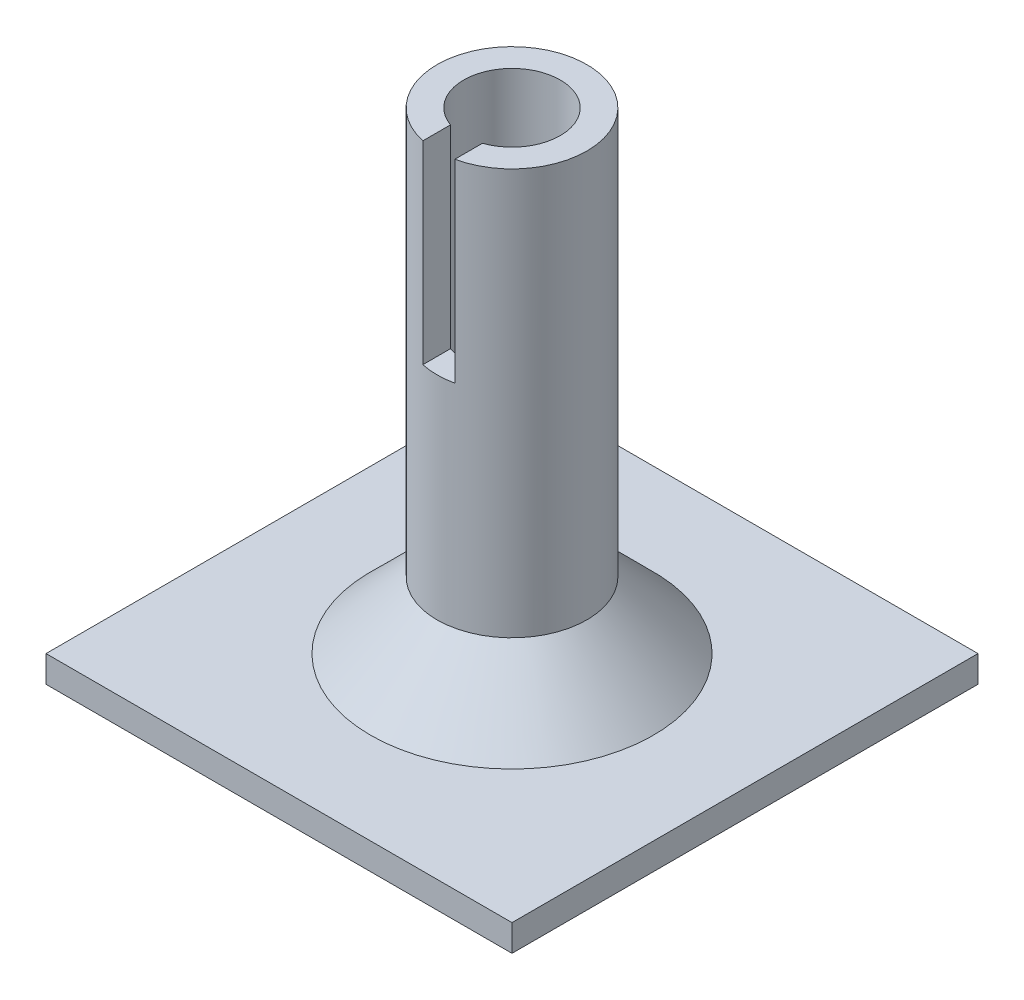
SolidWorks part; units mm, degrees
ref_plane "Front Plane" through (0, 0, 0) normal (0, 0, 1) x (1, 0, 0)
ref_plane "Top Plane" through (0, 0, 0) normal (0, 1, 0) x (1, 0, 0)
ref_plane "Right Plane" through (0, 0, 0) normal (1, 0, 0) x (0, 0, -1)
sketch "Sketch2" plane through (0, 0, 0) normal (0, 1, 0) x (1, 0, 0)
  line L1 (-35, 35) -> (35, 35)
  line L2 (-35, 35) -> (-35, -35)
  line L3 (-35, -35) -> (35, -35)
  line L4 (35, 35) -> (35, -35)
  circle A0 centre (0, 0) radius 7.25
  circle A1 centre (0, 0) radius 11.25
  point P8 (0, 0)
  point P9 (-25, 25)
  dimension "D1" = 70
  dimension "D4" = 14.5
  dimension "D5" = 22.5
  dimension "D2" = 35
  dimension "D3" = 35
extrude "Boss-Extrude1" add sketch "Sketch2" along normal blind 71 contours A0 | A1
extrude "Boss-Extrude2" add sketch "Sketch2<6>" against normal blind 4 contours L4 L1 L2 L3 A1 | A1 A0 | A0 region at (0, 0, -34.0101) region at (0, 0, 0) region at (-10.9318, 0, 0)
sketch "Sketch2<6>" plane through (0, 0, 0) normal (0, 1, 0) x (1, 0, 0) same geometry as "Sketch2"
chamfer "Chamfer1" distance 10 angle 45 1 edges at (0, 0, 11.25)
sketch "Sketch6" plane through (0, 0, 0) normal (0, 0, 1) x (1, 0, 0)
  line L0 (7.25, 71) -> (-7.25, 71) construction
  line L1 (-2.4, 71) -> (2.4, 71)
  line L2 (-2.4, 71) -> (-2.4, 41.8762)
  line L3 (-2.4, 41.8762) -> (2.4, 41.8762)
  line L4 (2.4, 71) -> (2.4, 41.8762)
  line L5 (-11.25, 71) -> (-11.25, 10) construction
  dimension "D1" = 4.8
  dimension "D2" = 8.85
extrude "Cut-Extrude2" cut sketch "Sketch6" along normal blind 25
